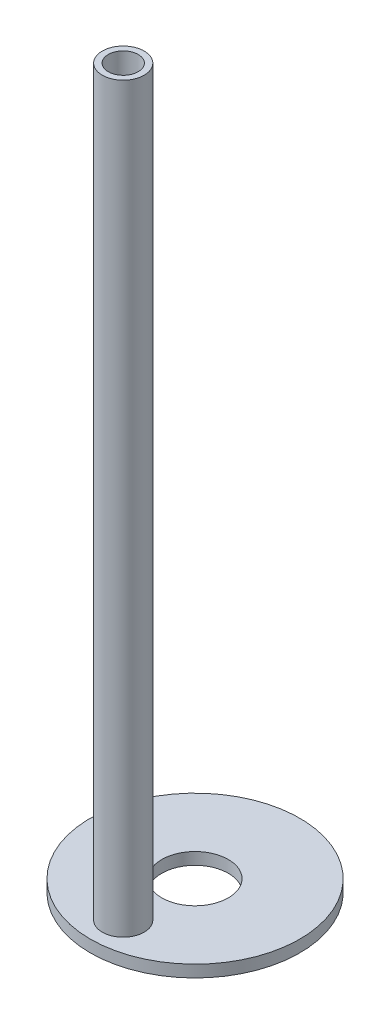
SolidWorks part; units mm, degrees
ref_plane "Front Plane" through (0, 0, 0) normal (0, 0, 1) x (1, 0, 0)
ref_plane "Top Plane" through (0, 0, 0) normal (0, 1, 0) x (1, 0, 0)
ref_plane "Right Plane" through (0, 0, 0) normal (1, 0, 0) x (0, 0, -1)
sketch "Sketch2" plane through (0, 0, 0) normal (0, 1, 0) x (1, 0, 0)
  line L0 (0, 1) -> (0, -1) construction
  line L1 (0, 0) -> (0, -12) construction
  circle A0 centre (0, 0) radius 17.5
  circle A2 centre (0, 0) radius 5.5562
  circle A3 centre (0, -12) radius 3.5
  point P8 (0, 0)
  dimension "D1" = 35
  dimension "D2" = 11.1125
  dimension "D3" = 12
  dimension "D6" = 7
  dimension "D4" = 2
extrude "Plate" add sketch "Sketch2" along normal mid plane 2 contours A0 A3 | A3 region at (-17.005, 0, 0) region at (0, 0, 12)
extrude "Rod" add sketch "Sketch2<4>" along normal blind 125 contours A3
sketch "Sketch2<4>" plane through (0, 0, 0) normal (0, 1, 0) x (1, 0, 0) same geometry as "Sketch2"
sketch "Sketch3" plane through (0, 125, 0) normal (0, 1, 0) x (1, 0, 0)
  circle A0 centre (0, -12) radius 2.5
  dimension "D1" = 5
extrude "Cut-Extrude1" cut sketch "Sketch3" against normal through all
